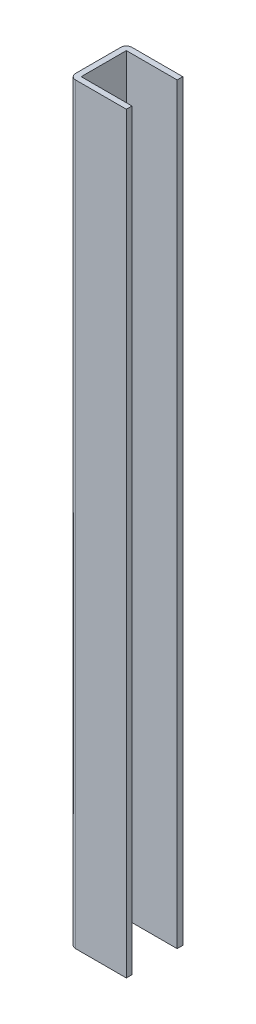
SolidWorks part; units mm, degrees
ref_plane "Спереди" through (0, 0, 0) normal (0, 0, 1) x (1, 0, 0)
ref_plane "Сверху" through (0, 0, 0) normal (0, 1, 0) x (1, 0, 0)
ref_plane "Справа" through (0, 0, 0) normal (1, 0, 0) x (0, 0, -1)
sketch "Эскиз1" plane through (0, 0, 0) normal (0, 1, 0) x (1, 0, 0)
  line L1 (-37, 15) -> (37, 15)
  line L2 (-40, 12) -> (-40, -12)
  line L3 (-37, -15) -> (37, -15)
  line L4 (40, 12) -> (40, -12)
  line L5 (-40, 15) -> (40, -15) construction
  line L6 (-40, -15) -> (40, 15) construction
  arc A0 (-37, 15) -> (-40, 12) centre (-37, 12) ccw
  arc A1 (-40, -12) -> (-37, -15) centre (-37, -12) ccw
  arc A2 (37, -15) -> (40, -12) centre (37, -12) ccw
  arc A3 (37, 15) -> (40, 12) centre (37, 12) cw
  point P0 (0, 0)
  dimension "D1" = 3
extrude "Вытянуть-Тонкостенный1" add sketch "Эскиз1" along normal blind 400 thin thin type one direction reverse wall 3
sketch "Эскиз2" plane through (0, 400, 0) normal (0, 1, 0) x (1, 0, 0)
  line L1 (-10, -23.0623) -> (41.1465, -23.0623)
  line L2 (-10, -23.0623) -> (-10, 20.9728)
  line L3 (-10, 20.9728) -> (41.1465, 20.9728)
  line L4 (41.1465, -23.0623) -> (41.1465, 20.9728)
extrude "Вырез-Вытянуть1" cut sketch "Эскиз2" against normal through all
